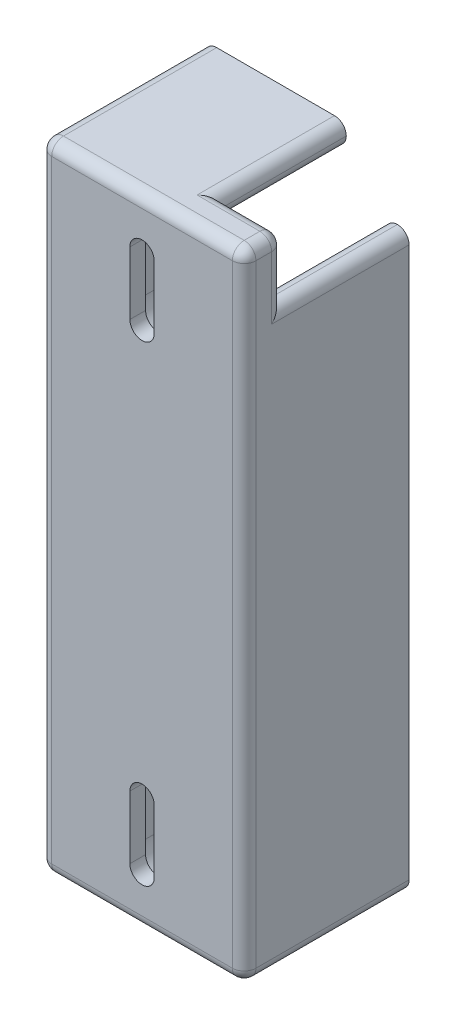
SolidWorks part; units mm, degrees
ref_plane "Front Plane" through (0, 0, 0) normal (0, 0, 1) x (1, 0, 0)
ref_plane "Top Plane" through (0, 0, 0) normal (0, 1, 0) x (1, 0, 0)
ref_plane "Right Plane" through (0, 0, 0) normal (1, 0, 0) x (0, 0, -1)
sketch "Sketch1" plane through (0, 0, 0) normal (0, 0, 1) x (1, 0, 0)
  line L0 (0.5, 15) -> (0.5, -60) construction
  line L1 (-9.5, -60) -> (10.5, -60)
  line L2 (-9.5, -60) -> (-9.5, 15)
  line L3 (-9.5, 15) -> (10.5, 15)
  line L5 (10.5, -60) -> (10.5, 15)
  line L6 (-9.5, -60) -> (10.5, 15) construction
  line L7 (-9.5, 15) -> (10.5, -60) construction
  line L8 (-12.5, -63) -> (-12.5, 18)
  line L13 (-12.5, 18) -> (13.5, 18)
  line L16 (13.5, -63) -> (13.5, 18)
  line L17 (-12.5, -63) -> (13.5, -63)
  dimension "D1" = 20
  dimension "D2" = 75
  dimension "D3" = 3
extrude "Boss-Extrude5" add sketch "Sketch1" along normal blind 16
sketch "Sketch7" plane through (0, 0, 16) normal (0, 0, 1) x (1, 0, 0)
  line L0 (0.5, 18) -> (0.5, -63) construction
  line L1 (-12.5, 18) -> (13.5, 18)
  line L2 (-12.5, 18) -> (-12.5, -63)
  line L3 (-12.5, -63) -> (13.5, -63)
  line L4 (13.5, 18) -> (13.5, -63)
  line L5 (-12.5, -22.5) -> (13.5, -22.5) construction
  line L6 (0.5, 11.5) -> (0.5, 3.5) construction
  line L7 (2.05, 11.5) -> (2.05, 3.5)
  line L8 (-1.05, 11.5) -> (-1.05, 3.5)
  line L9 (0.5, -56.5) -> (0.5, -48.5) construction
  line L10 (2.05, -56.5) -> (2.05, -48.5)
  line L11 (-1.05, -56.5) -> (-1.05, -48.5)
  arc A0 (2.05, 11.5) -> (-1.05, 11.5) centre (0.5, 11.5) ccw
  arc A1 (-1.05, 3.5) -> (2.05, 3.5) centre (0.5, 3.5) ccw
  arc A2 (2.05, -56.5) -> (-1.05, -56.5) centre (0.5, -56.5) cw
  arc A3 (-1.05, -48.5) -> (2.05, -48.5) centre (0.5, -48.5) cw
  point P12 (0.5, 7.5)
  point P17 (0, 0)
  point P20 (0.5, -52.5)
  dimension "D1" = 3.1
  dimension "D2" = 30
  dimension "D3" = 8
extrude "Boss-Extrude6" add sketch "Sketch7" along normal blind 5
sketch "Sketch8" plane through (0, 0, 16) normal (0, 0, -1) x (-1, 0, 0)
  line L0 (-0.5, 11.5) -> (-0.5, 3.5) construction
  line L1 (2.75, 11.5) -> (2.75, 3.5)
  line L2 (-3.75, 11.5) -> (-3.75, 3.5)
  line L3 (-10.5, -22.5) -> (9.5, -22.5) construction
  line L4 (-10.5, -60) -> (-10.5, 15) construction
  line L5 (9.5, 15) -> (9.5, -60) construction
  line L6 (-0.5, -56.5) -> (-0.5, -48.5) construction
  line L7 (2.75, -56.5) -> (2.75, -48.5)
  line L8 (-3.75, -56.5) -> (-3.75, -48.5)
  arc A0 (2.75, 11.5) -> (-3.75, 11.5) centre (-0.5, 11.5) ccw
  arc A1 (-3.75, 3.5) -> (2.75, 3.5) centre (-0.5, 3.5) ccw
  arc A2 (2.75, -56.5) -> (-3.75, -56.5) centre (-0.5, -56.5) cw
  arc A3 (-3.75, -48.5) -> (2.75, -48.5) centre (-0.5, -48.5) cw
  point P4 (-0.5, 7.5)
  point P17 (-0.5, -52.5)
  dimension "D1" = 6.5
extrude "Cut-Extrude3" cut sketch "Sketch8" against normal blind 3
sketch "Sketch9" plane through (0, 18, 0) normal (0, 1, 0) x (1, 0, 0)
  line L1 (13.5, 0) -> (5.5, 0)
  line L2 (13.5, 0) -> (13.5, -16)
  line L3 (13.5, -16) -> (5.5, -16)
  line L4 (5.5, 0) -> (5.5, -16)
  dimension "D1" = 16
  dimension "D2" = 8
extrude "Cut-Extrude4" cut sketch "Sketch9" against normal blind 8
fillet "Fillet3" radius 1.5 14 edges at (-12.5, -63, 10.5) (0.5, -63, 21) (13.5, -63, 10.5) (13.5, -22.5, 21) (9.5, 18, 16) (13.5, 14, 16) (-12.5, -22.5, 21) (10.5, 10, 8) (5.5, 15, 8) (5.5, 18, 8) (13.5, 10, 8) (13.5, 18, 18.5) (-12.5, 18, 10.5) (0.5, 18, 21)
